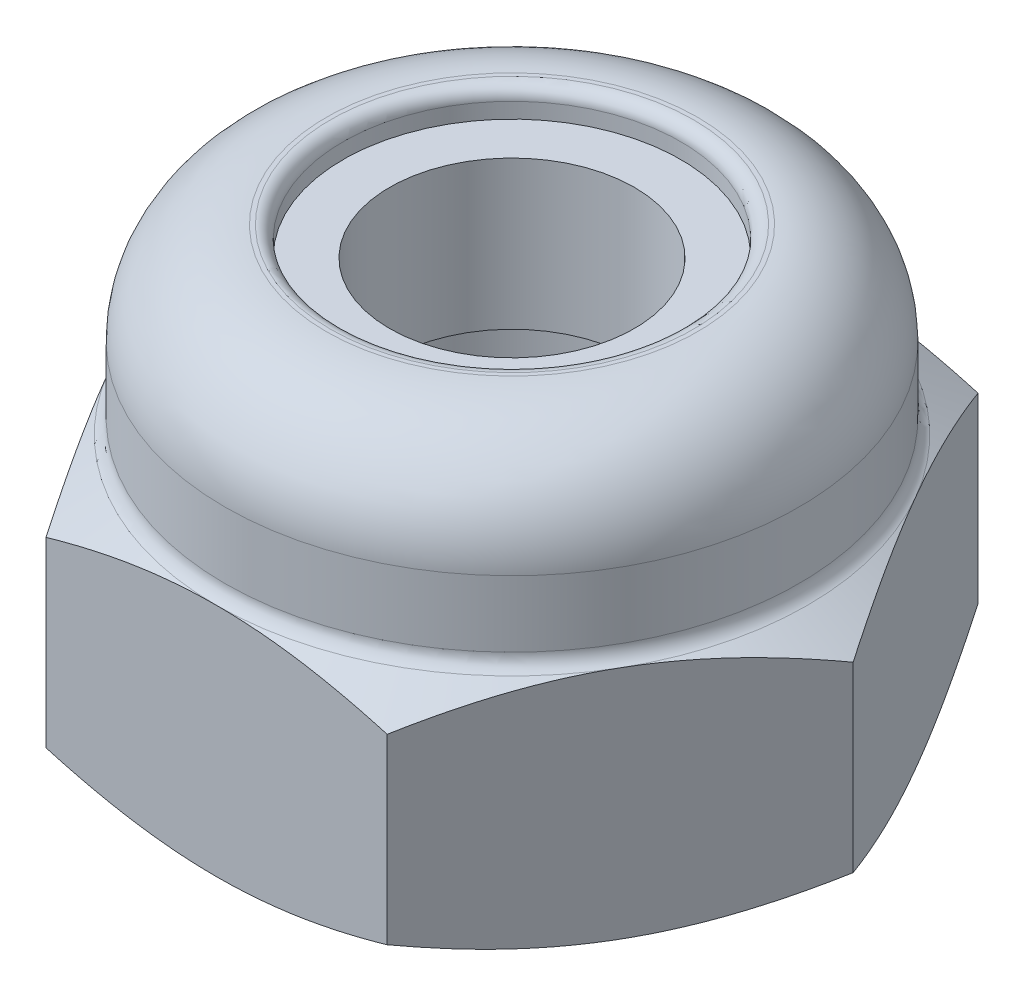
SolidWorks part; units mm, degrees
material "普通碳钢"
ref_plane "前视基准面" through (0, 0, 0) normal (0, 0, 1) x (1, 0, 0)
ref_plane "上视基准面" through (0, 0, 0) normal (0, 1, 0) x (1, 0, 0)
ref_plane "右视基准面" through (0, 0, 0) normal (1, 0, 0) x (0, 0, -1)
sketch "草图1" plane through (0, 0, 0) normal (0, 1, 0) x (1, 0, 0)
  line L1 (4.0415, 0) -> (2.0207, 3.5)
  line L2 (2.0207, 3.5) -> (-2.0207, 3.5)
  line L3 (-2.0207, 3.5) -> (-4.0415, 0)
  line L4 (-4.0415, 0) -> (-2.0207, -3.5)
  line L5 (-2.0207, -3.5) -> (2.0207, -3.5)
  line L6 (2.0207, -3.5) -> (4.0415, 0)
  circle A0 centre (0, 0) radius 3.5 construction
  circle A1 centre (0, 0) radius 1.65
  dimension "D2" = 3.3
extrude "凸台-拉伸1" add sketch "草图1" along normal mid plane 2.9
sketch "草图4" plane through (0, 0, 0) normal (1, 0, 0) x (0, 0, -1)
  line L0 (0, 2.8045) -> (0, -1.6258) construction
  line L1 (-3.4, 1.45) -> (-3.4, 3.55)
  line L2 (0, 1.45) -> (-3.5, 1.45) construction
  line L3 (-3.4, 3.55) -> (-2, 3.55)
  line L4 (-2, 3.55) -> (-2, 3.2167)
  line L5 (-2, 3.2167) -> (-2.5, 3.2167)
  line L6 (-2.5, 3.2167) -> (-2.5, 1.45)
  line L7 (-2.5, 1.45) -> (-3.4, 1.45)
  line L8 (0, -1.45) -> (-3.5, -1.45) construction
  dimension "D1" = 6.8
  dimension "D2" = 5
  dimension "D3" = 5
  dimension "D4" = 0.3333
  dimension "D5" = 4
revolve "旋转1" add sketch "草图4" angle 360 about L0
sketch "草图5" plane through (0, 0, 0) normal (1, 0, 0) x (0, 0, -1)
  line L0 (0, 2.5136) -> (0, -1.2831) construction
  line L1 (-3.5, 1.45) -> (0, 1.45) construction
  line L2 (-2.5, 3.2067) -> (-1.45, 3.2067)
  line L3 (-2.5, 3.2067) -> (-2.5, 1.45)
  line L4 (-2.5, 1.45) -> (-1.45, 1.45)
  line L5 (-1.45, 3.2067) -> (-1.45, 1.45)
  line L6 (-2.5, 3.2167) -> (-2.5, 1.45) construction
  line L7 (-2, 3.2167) -> (-2.5, 3.2167) construction
  dimension "D1" = 2.9
revolve "旋转2" add sketch "草图5" angle 360 about L0
fillet "圆角1" radius 1.2 1 edges at (0, 3.55, 3.4)
fillet "圆角3" radius 0.15 1 edges at (0, 3.55, 2)
sketch "草图6" plane through (0, 0, 0) normal (1, 0, 0) x (0, 0, -1)
  line L0 (0, 2.5376) -> (0, -1.7712) construction
  line L1 (-2.5233, 0) -> (2.9538, 0) construction
  line L2 (3.4, 1.45) -> (5.8249, 1.45)
  line L3 (5.8249, 1.45) -> (5.8249, 0.05)
  line L4 (5.8249, 0.05) -> (3.4, 1.45)
  line L5 (5.8249, -0.05) -> (3.4, -1.45)
  line L6 (5.8249, -1.45) -> (5.8249, -0.05)
  line L7 (3.4, -1.45) -> (5.8249, -1.45)
  line L9 (3.5, 1.45) -> (3.5, -1.45) construction
  line L10 (-3.5, 1.45) -> (0, 1.45) construction
  dimension "D1" = 30
  dimension "D2" = 0.1
  dimension "D3" = 0.1
revolve "切除-旋转1" cut sketch "草图6" angle 360 about L0
fillet "圆角4" radius 0.2 1 edges at (0, 1.45, 3.4)
fillet "圆角5" radius 0.3 1 edges at (0, -1.45, 3.4)
chamfer "倒角1" [suppressed] distance 0.1 angle 45
move or copy body "实体-移动/复制3" [suppressed] bodies to move or copy 109
move or copy body "实体-移动/复制4" [suppressed] bodies to move or copy 112
move or copy body "实体-移动/复制2" [suppressed] bodies to move or copy 109
move or copy body "实体-移动/复制1" [suppressed] bodies to move or copy 109
equation "\"规格\"= 2"
equation "\"螺距\"= 0.4"
equation "\"孔径\"= \"规格\" - \"螺距\""
equation "\"h\"= 3"
equation "\"m\"= 2"
equation "\"s\"= 4"
equation "\"D1@草图1\"=\"s\""
equation "\"D2@草图1\"=\"孔径\""
equation "\"D1@凸台-拉伸1\"=\"m\""
equation "\"D1@草图4\"=\"s\"-0.2"
equation "\"D2@草图4\"=\"h\""
equation "\"D3@草图4\"=\"规格\"+1"
equation "\"D4@草图4\"=\"h\"/15"
equation "\"D5@草图4\"=\"规格\"+0.2"
equation "\"D1@草图5\"=\"规格\"-0.6"
